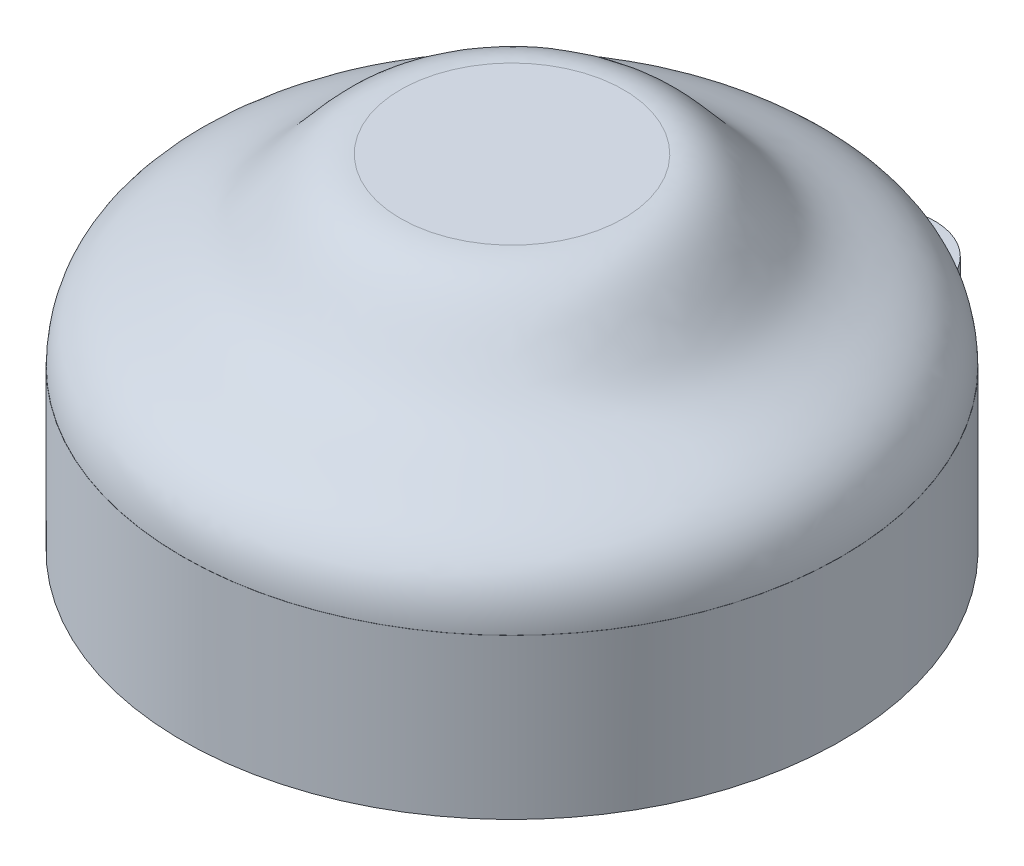
SolidWorks part; units mm, degrees
ref_plane "Front Plane" through (0, 0, 0) normal (0, 0, 1) x (1, 0, 0)
ref_plane "Top Plane" through (0, 0, 0) normal (0, 1, 0) x (1, 0, 0)
ref_plane "Right Plane" through (0, 0, 0) normal (1, 0, 0) x (0, 0, -1)
sketch "Sketch3" plane through (0, 0, 0) normal (0, 1, 0) x (1, 0, 0)
  circle A0 centre (0, 0) radius 26.128
  circle A1 centre (0, 0) radius 26.878
extrude "Boss-Extrude1" add sketch "Sketch3" along normal blind 13
sketch "Sketch4" plane through (0, 13, 0) normal (0, 1, 0) x (1, 0, 0)
  circle A0 centre (0, 0) radius 26.878
sketch "Sketch5" plane through (0, 0, 0) normal (0, -1, 0) x (1, 0, 0)
  line L0 (-5.5432, -29.9954) -> (-5.5432, -26.3002)
  line L1 (4.4919, -29.9954) -> (4.4919, -26.5)
  arc A0 (-5.5432, -29.9954) -> (4.4919, -29.9954) centre (-0.5256, -29.9954) ccw
  circle A1 centre (0, 0) radius 26.878 construction
  arc A2 (-5.5432, -26.3002) -> (4.4919, -26.5) centre (0.0111, 0.5595) ccw
  circle A3 centre (-0.5256, -29.9954) radius 1.65
  dimension "D1" = 30
extrude "Boss-Extrude4" add sketch "Sketch5" against normal blind 5.5
sketch "Sketch6" plane through (0, 0, 0) normal (0, -1, 0) x (-1, 0, 0)
  line L0 (4.7101, 29.9954) -> (4.7101, 25.6999)
  line L1 (-3.6589, 29.9954) -> (-3.6589, 25.8176)
  arc A0 (4.7101, 29.9954) -> (-3.6589, 29.9954) centre (0.5256, 29.9954) ccw
  circle A1 centre (0, 0) radius 26.128 construction
  arc A3 (4.7101, 25.6999) -> (-3.6589, 25.8176) centre (0.1631, -0.0266) ccw
extrude "Cut-Extrude1" cut sketch "Sketch6" against normal blind 3.5
ref_axis "Center" through (0, 30.1875, 0) along (0, -1, 0)
sketch "Sketch8" plane through (0, 0, 0) normal (0, -1, 0) x (1, 0, 0)
  line L2 (-24.4903, -5.0225) -> (-25.5997, -5.25)
  line L3 (24.4903, -5.0225) -> (25.5997, -5.25)
  arc A0 (-25.5997, -5.25) -> (25.5997, -5.25) centre (0, 0) ccw
  arc A1 (-24.4903, -5.0225) -> (24.4903, -5.0225) centre (0, 0) ccw
  dimension "D1" = 5.25
extrude "Boss-Extrude5" add sketch "Sketch8" against normal blind 1.5 from offset 3.5 offset against normal yes
sketch "Sketch9" plane through (0, 0, 0) normal (0, 0, 1) x (1, 0, 0)
  line L0 (0, 28) -> (-9.1011, 28)
  line L1 (0, 30.1875) -> (0, -1.4375) construction
  line L2 (26.128, 13) -> (-26.128, 13) construction
  line L3 (26.878, 13) -> (-26.878, 13) construction
  line L4 (-8.9709, 27.25) -> (0, 27.25)
  line L5 (0, 27.25) -> (0, 28)
  line L6 (-26.8652, 13) -> (-26.0776, 13)
  spline S0 degree 3 poles (-26.8652, 13) (-26.7803, 19.1839) (-16.2707, 18.7257) (-13.0028, 28.0264) (-9.1011, 28) knots 0 0 0 0 0.568593 1 1 1 1
  spline S1 degree 3 poles (-26.0776, 13) (-26.0086, 18.6883) (-15.7421, 18.4988) (-12.7222, 27.2856) (-8.9709, 27.25) knots 0 0 0 0 0.575101 1 1 1 1
  dimension "D1" = 15
  dimension "D3" = 0.75
revolve "Revolve2" add sketch "Sketch9" angle 360 about axis through (0, 30.1875, 0) along (0, -1, 0)
fillet "Fillet1" radius 5 4 edges at (3.6589, 1.75, -25.8705) (4.4919, 2.75, -26.5) (-5.5432, 2.75, -26.3002) (-4.7101, 1.75, -25.6999)
